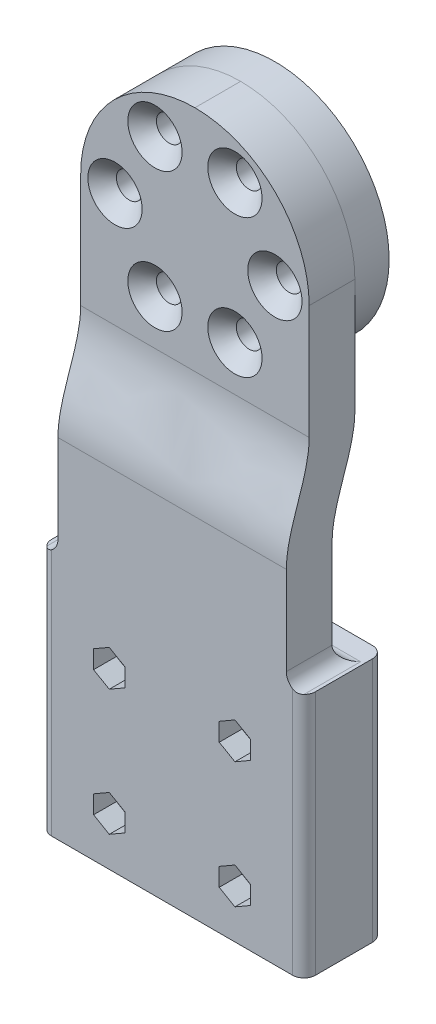
SolidWorks part; units mm, degrees
other "Markup1"
sketch "Sketch13" plane through (20, -53, 11) normal (0.0614, -0.6805, 0.7302) x (0.9699, -0.1321, -0.2046)
sketch "Sketch25" plane through (23.1, -99, 18.0001) normal (0.0614, -0.6805, 0.7302) x (0.9699, -0.1321, -0.2046)
ref_plane "Front Plane" through (0, 0, 0) normal (0, 0, 1) x (1, 0, 0)
ref_plane "Top Plane" through (0, 0, 0) normal (0, 1, 0) x (1, 0, 0)
ref_plane "Right Plane" through (0, 0, 0) normal (1, 0, 0) x (0, 0, -1)
sketch "Sketch7" plane through (0, 0, 0) normal (0, 0, 1) x (1, 0, 0)
  line L1 (-20, 20) -> (20, 20)
  line L2 (-20, 20) -> (-20, -20)
  line L3 (-20, -20) -> (20, -20)
  line L4 (20, 20) -> (20, -20)
  line L5 (-20, 20) -> (20, -20) construction
  line L6 (-20, -20) -> (20, 20) construction
  point P0 (0, 0)
extrude "Boss-Extrude1" add sketch "Sketch7" along normal blind 14
ref_plane "Plane2" through (0, -22.1603, 5.9378) normal (0, -0.9659, 0.2588) x (1, 0, 0)
sketch "Sketch8" plane through (0, -20, 2.0782) normal (0, -1, 0) x (1, 0, 0)
  line L0 (20, 11.9218) -> (20, -2.0782) construction
  line L1 (-20, 11.9218) -> (20, 11.9218)
  line L2 (-20, 11.9218) -> (-20, 3.9218)
  line L3 (-20, 3.9218) -> (20, 3.9218)
  line L4 (20, 11.9218) -> (20, 3.9218)
  line L5 (0, 3.9218) -> (0, 11.9218) construction
  line L6 (-20, 7.9218) -> (20, 7.9218) construction
  line L7 (-20, -2.0782) -> (20, -2.0782) construction
  point P764 (0, 7.9218)
  dimension "D1" = 6
ref_plane "Plane4" through (0, -38, 0) normal (0, -1, 0) x (-1, 0, 0)
sketch "Sketch19" plane through (0, -38, 0) normal (0, -1, 0) x (-1, 0, 0)
  line L5 (20, -10) -> (-20, -10) construction
  line L6 (20, -18) -> (-20, -18)
  line L10 (20, -18) -> (20, -10)
  line L11 (20, -10) -> (-20, -10)
  line L12 (-20, -18) -> (-20, -10)
  line L13 (20, -18) -> (-20, -10) construction
  line L14 (20, -10) -> (-20, -18) construction
  line L16 (20, -14) -> (20, 0) construction
  point P0 (0, -14)
  dimension "D1" = 40
  dimension "D2" = 8
  dimension "D3" = 4
loft "Loft1" add profiles "Sketch19", "Sketch8<3>" start constraint normal to profile start tangent length 1 end constraint normal to profile end tangent length 1 connector at (-20, -38, 18) connector at (-20, -20, 14)
sketch "Sketch8<3>" plane through (0, -20, 2.0782) normal (0, -1, 0) x (1, 0, 0) same geometry as "Sketch8"
sketch "Sketch16" plane through (0, 0, 0) normal (0, 0, -1) x (-1, 0, 0)
  line L1 (24.5131, 32.6211) -> (-24.5131, 32.6211)
  line L2 (24.5131, 32.6211) -> (24.5131, -32.6211)
  line L3 (24.5131, -32.6211) -> (-24.5131, -32.6211)
  line L4 (-24.5131, 32.6211) -> (-24.5131, -32.6211)
  line L5 (24.5131, 32.6211) -> (-24.5131, -32.6211) construction
  line L6 (24.5131, -32.6211) -> (-24.5131, 32.6211) construction
  circle A0 centre (0, 0) radius 20
extrude "Cut-Extrude3" cut sketch "Sketch16" against normal blind 6
ref_plane "Plane3" [suppressed] through (0, -56, 0) normal (0, -1, 0) x (-1, 0, 0)
sketch "Sketch17" plane through (0, -38, 0) normal (0, -1, 0) x (-1, 0, 0)
  line L1 (20, -18) -> (-20, -18)
  line L2 (20, -18) -> (20, -10)
  line L3 (20, -10) -> (-20, -10)
  line L4 (-20, -18) -> (-20, -10)
  line L5 (20, -18) -> (-20, -10) construction
  line L6 (20, -10) -> (-20, -18) construction
  line L7 (-20, -18) -> (20, -18) construction
  line L11 (-20, -6) -> (-20, -10) construction
  line L12 (20, -14) -> (20, -6) construction
  point P4 (0, -14)
  dimension "D1" = 8
extrude "Boss-Extrude5" add sketch "Sketch17" along normal blind 18
sketch "Sketch10" plane through (0, 0, 14) normal (0, 0, 1) x (1, 0, 0)
  circle A0 centre (-7.0001, 12.1244) radius 2.25
  circle A1 centre (6.9999, 12.1244) radius 2.25
  circle A2 centre (13.9999, 0.0001) radius 2.25
  circle A3 centre (6.9999, -12.1243) radius 2.25
  circle A4 centre (-7.0001, -12.1243) radius 2.25
  circle A5 centre (-14.0001, 0.0001) radius 2.25
  point P0 (0, 0)
  point P1 (0.0025, 0.0011)
  dimension "D4" = 4.5
extrude "Cut-Extrude1" cut sketch "Sketch10" against normal blind 25
sketch "Sketch11" plane through (0, -56, -3.473) normal (0, 1, 0) x (1, 0, 0)
  line L0 (20, -21.473) -> (-20, -21.473) construction
  line L5 (23.1, -7.473) -> (-23.1, -7.473)
  line L6 (23.1, -7.473) -> (23.1, -21.473)
  line L7 (23.1, -21.473) -> (-23.1, -21.473)
  line L8 (-23.1, -7.473) -> (-23.1, -21.473)
  line L9 (23.1, -7.473) -> (-23.1, -21.473) construction
  line L10 (23.1, -21.473) -> (-23.1, -7.473) construction
  line L16 (20, -13.473) -> (20, -21.473) construction
  point P0 (0, -14.473)
  dimension "D1" = 46.2
  dimension "D2" = 3.1
  dimension "D3" = 14
chamfer "Chamfer1" distance 2.5 angle 45 6 edges at (-4.7501, 12.1244, 14) (-11.7501, 0.0001, 14) (-4.7501, -12.1243, 14) (9.2499, 12.1244, 14) (16.2499, 0.0001, 14) (9.2499, -12.1243, 14)
fillet "Fillet3" radius 20 2 edges at (20, 20, 10) (-20, 20, 10)
extrude "Boss-Extrude6" add sketch "Sketch11" against normal blind 43
fillet "Fillet9" radius 2.5 3 edges at (0, -56, 10) (-20, -56, 14) (20, -56, 14)
ref_plane "Plane5" through (0, -99, 0) normal (0, -1, 0) x (-1, 0, 0)
sketch "Sketch20" plane through (0, -99, 0) normal (0, -1, 0) x (1, 0, 0)
  line L0 (0, 4) -> (0, 18) construction
  line L1 (20.3, 8.8) -> (-20.3, 8.8)
  line L2 (20.3, 8.8) -> (20.3, 13.2)
  line L3 (20.3, 13.2) -> (-20.3, 13.2)
  line L4 (-20.3, 8.8) -> (-20.3, 13.2)
  line L5 (20.3, 8.8) -> (-20.3, 13.2) construction
  line L6 (20.3, 13.2) -> (-20.3, 8.8) construction
  line L7 (23.1, 4) -> (-23.1, 4) construction
  line L8 (-23.1, 18) -> (23.1, 18) construction
  line L9 (-23.1, 4) -> (-23.1, 18) construction
  point P0 (0, 11)
  dimension "D1" = 4.4
  dimension "D2" = 40.6
  dimension "D3" = 23.1
  dimension "D4" = 7
extrude "Cut-Extrude4" cut sketch "Sketch20" against normal blind 40
sketch "Sketch22" plane through (0, 0, 0) normal (0, 0, 1) x (1, 0, 0)
  line L0 (-7.7, -99) -> (7.7, -99) construction
  line L1 (20, -99) -> (-20, -99)
  line L2 (20, -99) -> (20, -59)
  line L3 (20, -59) -> (-20, -59)
  line L4 (-20, -99) -> (-20, -59)
  line L5 (20, -99) -> (-20, -59) construction
  line L6 (20, -59) -> (-20, -99) construction
  line L9 (23.1, -99) -> (23.1, -56) construction
  circle A0 centre (-11, -68.5) radius 1.7
  circle A1 centre (11, -68.5) radius 1.7
  circle A2 centre (11, -90.5) radius 1.7
  circle A3 centre (-11, -90.5) radius 1.7
  point P0 (0, -79)
  dimension "D4" = 3.4
  dimension "D1" = 40
  dimension "D2" = 40
  dimension "D3" = 23.1
  dimension "D5" = 9.5
  dimension "D6" = 8.5
  dimension "D7" = 9
  dimension "D8" = 9
  dimension "D9" = 8.5
  dimension "D10" = 9
  dimension "D11" = 22
extrude "Cut-Extrude5" cut sketch "Sketch22" along normal blind 30 contours A1 | A2 | A3 | A0 region at (-11, -68.5, 0) region at (11, -68.5, 0) region at (11, -90.5, 0) region at (-11, -90.5, 0)
fillet "Fillet11" radius 2 4 edges at (-23.1, -77.5, 18) (-23.1, -77.5, 4) (23.1, -77.5, 18) (23.1, -77.5, 4)
ref_plane "Plane6" through (0, 0, 18) normal (0, 0, 1) x (1, 0, 0)
sketch "Sketch23" plane through (0, 0, 18) normal (0, 0, 1) x (1, 0, 0)
  line L0 (-13.75, -66.9123) -> (-8.25, -70.0877) construction
  line L1 (-11, -65.3246) -> (-13.75, -66.9123)
  line L2 (-13.75, -66.9123) -> (-13.75, -70.0877)
  line L3 (-13.75, -70.0877) -> (-11, -71.6754)
  line L4 (-11, -71.6754) -> (-8.25, -70.0877)
  line L5 (-8.25, -70.0877) -> (-8.25, -66.9123)
  line L6 (-8.25, -66.9123) -> (-11, -65.3246)
  line L7 (-11, -65.3246) -> (-11, -71.6754) construction
  line L8 (11, -65.3246) -> (11, -71.6754) construction
  line L9 (11, -65.3246) -> (8.25, -66.9123)
  line L10 (8.25, -66.9123) -> (8.25, -70.0877)
  line L11 (8.25, -70.0877) -> (11, -71.6754)
  line L12 (11, -71.6754) -> (13.75, -70.0877)
  line L13 (13.75, -70.0877) -> (13.75, -66.9123)
  line L14 (13.75, -66.9123) -> (11, -65.3246)
  line L15 (11, -87.3246) -> (8.25, -88.9123)
  line L16 (8.25, -88.9123) -> (8.25, -92.0877)
  line L17 (8.25, -92.0877) -> (11, -93.6754)
  line L18 (11, -93.6754) -> (13.75, -92.0877)
  line L19 (13.75, -92.0877) -> (13.75, -88.9123)
  line L20 (13.75, -88.9123) -> (11, -87.3246)
  line L21 (-11, -87.3246) -> (-13.75, -88.9123)
  line L22 (-13.75, -88.9123) -> (-13.75, -92.0877)
  line L23 (-13.75, -92.0877) -> (-11, -93.6754)
  line L24 (-11, -93.6754) -> (-8.25, -92.0877)
  line L25 (-8.25, -92.0877) -> (-8.25, -88.9123)
  line L26 (-8.25, -88.9123) -> (-11, -87.3246)
  line L27 (11, -87.3246) -> (11, -94.13) construction
  line L28 (-11, -87.3246) -> (-11, -93.6754) construction
  circle A0 centre (-11, -68.5) radius 2.75 construction
  circle A1 centre (11, -68.5) radius 2.75 construction
  circle A2 centre (11, -90.5) radius 2.75 construction
  circle A3 centre (-11, -90.5) radius 2.75 construction
  point P28 (-13.75, -90.5)
  dimension "D1" = 5.5
  dimension "D2" = 60
  dimension "D3" = 5.5
  dimension "D4" = 5.5
  dimension "D5" = 5.5
extrude "Cut-Extrude6" cut sketch "Sketch23" against normal blind 4
ref_plane "Plane7" through (0, 0, 4) normal (0, 0, -1) x (-1, 0, 0)
sketch "Sketch24" plane through (0, 0, 4) normal (0, 0, -1) x (-1, 0, 0)
  circle A0 centre (-11, -68.5) radius 3
  circle A1 centre (11, -68.5) radius 3
  circle A2 centre (11, -90.5) radius 3
  circle A3 centre (-11, -90.5) radius 3
  dimension "D1" = 6
  dimension "D2" = 6
  dimension "D3" = 6
  dimension "D4" = 6
extrude "Cut-Extrude7" cut sketch "Sketch24" against normal blind 3 contours A1 | A2 | A3 | A0
